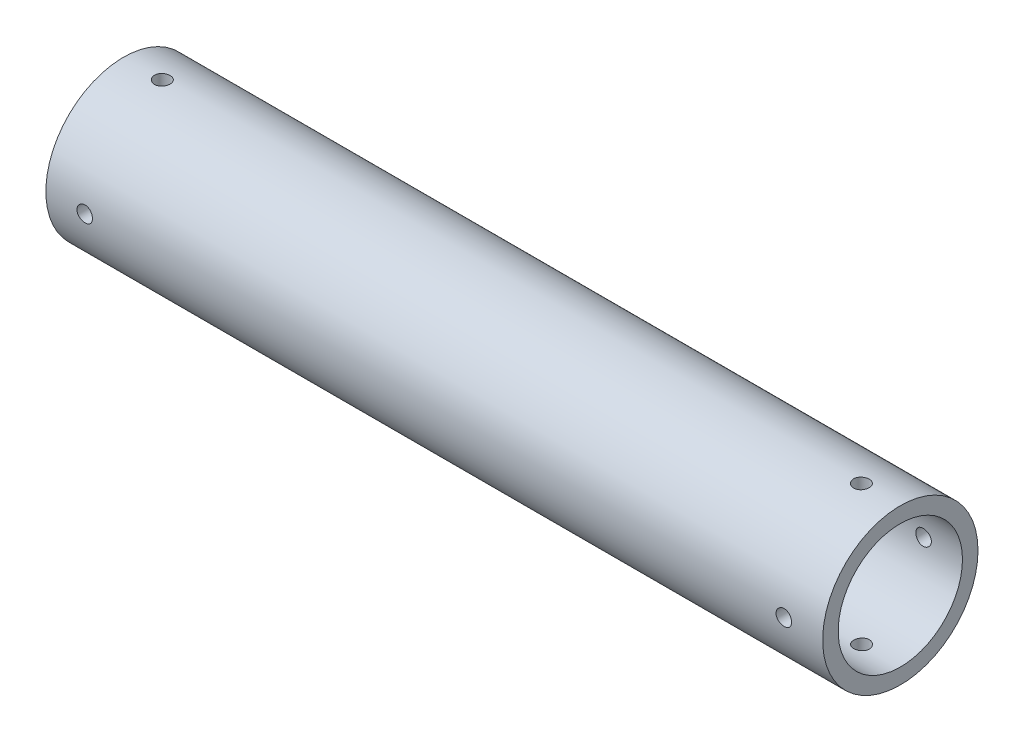
SolidWorks part; units mm, degrees
material "Zoltek Panex 33"
ref_plane "Спереди" through (0, 0, 0) normal (0, 0, 1) x (1, 0, 0)
ref_plane "Сверху" through (0, 0, 0) normal (0, 1, 0) x (1, 0, 0)
ref_plane "Справа" through (0, 0, 0) normal (1, 0, 0) x (0, 0, -1)
other "Configuration Table"
sketch "Эскиз2" plane through (0, 0, 0) normal (1, 0, 0) x (0, 0, -1)
  circle A0 centre (0, 0) radius 20
  circle A1 centre (0, 0) radius 16
  dimension "D1" = 40
  dimension "D2" = 32
extrude "Бобышка-Вытянуть2" add sketch "Эскиз2" along normal blind 200
ref_plane "Плоскость1" through (0, 0, 25) normal (0, 0, 1) x (1, 0, 0)
sketch "Эскиз4" plane through (0, 0, 25) normal (0, 0, 1) x (1, 0, 0)
  line L0 (0, -20) -> (200, -20) construction
  line L1 (200, -20) -> (200, 20) construction
  circle A0 centre (10, 0) radius 2
  circle A1 centre (190, 0) radius 2
  dimension "D1" = 4
  dimension "D4" = 4
  dimension "D2" = 10
  dimension "D3" = 20
  dimension "D5" = 10
extrude "Вырез-Вытянуть2" cut sketch "Эскиз4" against normal blind 10 and the other way blind 10 contours A0 | A1
pattern_circular "Круговой массив1" count 4 over 360 about axis through (200, 0, 0) along (-1, 0, 0) of "Вырез-Вытянуть2"
equation "\"Diameter\" = 40мм"
equation "\"D1@Эскиз2\"= \"Diameter\""
equation "\"Length\"= 200мм"
equation "\"Thickness\"= 4мм"
equation "\"D1@Бобышка-Вытянуть2\"= \"Length\""
equation "\"D2@Эскиз2\" = \"Diameter\" - \"Thickness\" * 2"
equation "\"D4@Эскиз4\"=\"D1@Эскиз4\""
equation "\"D5@Эскиз4\"=\"D2@Эскиз4\""
equation "\"D3@Эскиз4\"=\"Diameter\"/2"
